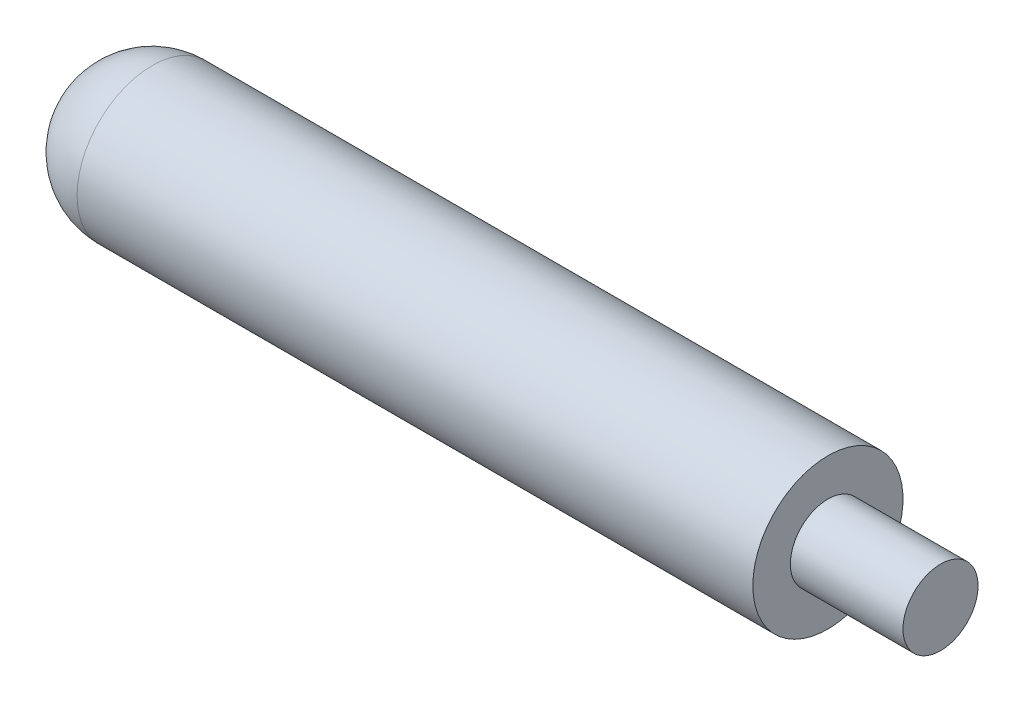
SolidWorks part; units mm, degrees
ref_plane "Front Plane" through (0, 0, 0) normal (0, 0, 1) x (1, 0, 0)
ref_plane "Top Plane" through (0, 0, 0) normal (0, 1, 0) x (1, 0, 0)
ref_plane "Right Plane" through (0, 0, 0) normal (1, 0, 0) x (0, 0, -1)
ref_axis "Axis1" through (-88.99, 0, 0) along (1, 0, 0)
sketch "Sketch2" plane through (0, 0, 0) normal (0, 0, 1) x (1, 0, 0)
  line L0 (0, -55) -> (0, 55) construction
  line L1 (55, 0) -> (-55, 0) construction
  line L2 (0, 0) -> (146.05, 0)
  line L3 (146.05, 0) -> (146.05, 6.35)
  line L4 (146.05, 6.35) -> (127, 6.35)
  line L5 (127, 6.35) -> (127, 12.7)
  line L6 (127, 12.7) -> (12.7, 12.7)
  arc A0 (12.7, 12.7) -> (0, 0) centre (12.7, 0) ccw
  point P0 (0, 0)
  dimension "D1" = 19.05
  dimension "D2" = 146.05
  dimension "D3" = 12.7
  dimension "D4" = 6.35
revolve "Revolve1" add sketch "Sketch2" angle 360 about L2
ref_plane "Plane1" through (146.05, 0, 0) normal (1, 0, 0) x (0, 0, -1)
